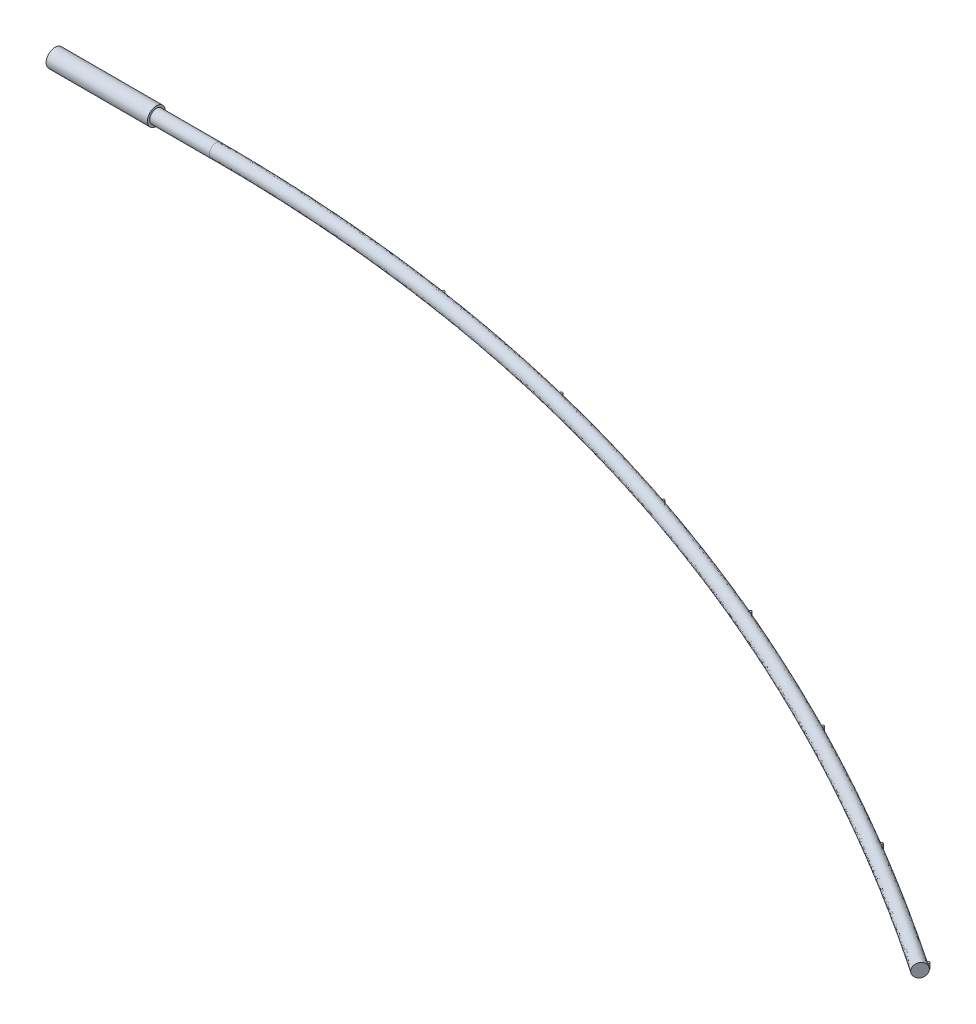
SolidWorks part; units mm, degrees
ref_plane "Front Plane" through (0, 0, 0) normal (0, 0, 1) x (1, 0, 0)
ref_plane "Top Plane" through (0, 0, 0) normal (0, 1, 0) x (1, 0, 0)
ref_plane "Right Plane" through (0, 0, 0) normal (1, 0, 0) x (0, 0, -1)
sketch "Sketch2" plane through (0, 0, 0) normal (1, 0, 0) x (0, 0, -1)
  circle A0 centre (0, 0) radius 1.5
  dimension "D1" = 3
extrude "Boss-Extrude1" add sketch "Sketch2" against normal blind 17
sketch "Sketch4" plane through (0, 0, 0) normal (0, 1, 0) x (1, 0, 0)
  line L0 (0, 0) -> (10, 0)
  dimension "D1" = 10
sketch "Sketch5" plane through (0, 0, 0) normal (1, 0, 0) x (0, 0, -1)
  line L0 (0, 0) -> (0, 1.125) construction
  circle A0 centre (0, 0) radius 1.125
  dimension "D1" = 1.125
sweep "Sweep2" add profiles "Sketch5" path "Sketch4"
sketch "Sketch3" plane through (0, 0, 0) normal (0, 1, 0) x (1, 0, 0)
  line L1 (10, -1.125) -> (10, 1.125) construction
  spline S0 degree 2 poles (-7.7999, -0.6016) (97.9101, 6.535) (203.6272, -70.9884) knots 0 0 0 1 1 1 construction
  spline S1 degree 2 poles (10, 0) (99, 0.0075) (188.005, -59.9946) knots 0.084192 0.084192 0.084192 0.926113 0.926113 0.926113
sketch "Sketch1" plane through (10, 0, 0) normal (1, 0, 0) x (0, 0, -1)
  line L0 (0, 0) -> (0, 1.125) construction
  circle A0 centre (0, 0) radius 1.125
  dimension "D1" = 1.125
sweep "Sweep3" add profiles "Sketch1" path "Sketch3"
sketch "Sketch6" plane through (0, 0, 0) normal (0, 1, 0) x (1, 0, 0)
  line L0 (50.0173, -1.8928) -> (49.6818, -4.1158)
  line L1 (98.7348, -13.7208) -> (98.022, -15.8507)
  line L2 (144.9161, -33.2009) -> (143.8965, -35.2041)
  line L3 (188.063, -58.6775) -> (186.8081, -60.5451)
  line L4 (74.6352, -6.7507) -> (74.1032, -8.9334)
  line L5 (122.1884, -22.608) -> (121.3129, -24.6769)
  line L6 (166.8766, -45.2889) -> (165.7309, -47.2245)
  circle A0 centre (50.0173, -1.8928) radius 0.2
  circle A1 centre (98.7348, -13.7208) radius 0.2
  circle A2 centre (144.9161, -33.2009) radius 0.2
  circle A3 centre (188.063, -58.6775) radius 0.2
  circle A4 centre (74.6352, -6.7507) radius 0.2
  circle A5 centre (122.1884, -22.608) radius 0.2
  circle A6 centre (166.8766, -45.2889) radius 0.2
  spline S0 degree 3 poles (188.634, -59.0618) (129.1532, -18.9633) (69.5862, 1.13) (10, 1.125) knots 0 0 0 0 1 1 1 1 weights 1 1 1 1 construction
  spline S1 degree 3 poles (10, -1.125) (69.0805, -1.12) (128.1835, -21.0232) (187.3761, -60.9274) knots 0 0 0 0 1 1 1 1 weights 1 1 1 1 construction
  point P0 (49.849, -3.008)
  point P9 (98.376, -14.793)
  point P12 (187.427, -59.624)
  point P16 (144.401, -34.213)
  point P20 (74.368, -7.847)
  point P23 (121.747, -23.651)
  point P28 (166.297, -46.268)
  dimension "D1" = 0.4
  dimension "D2" = 0.4
  dimension "D3" = 0.4
  dimension "D4" = 0.4
  dimension "D5" = 0.4
  dimension "D6" = 0.4
  dimension "D7" = 0.4
extrude "Boss-Extrude2" add sketch "Sketch6" along normal blind 0.5 and the other way blind 0.5 contours A1 | A0 | A2 | A3 | A4 | A5 | A6 region at (50.144, 0, 2.0401) region at (98.8484, 0, 13.8785) region at (145.0177, 0, 33.3666) region at (188.1544, 0, 58.8491) region at (74.7553, 0, 6.9035) region at (122.2957, 0, 22.77) region at (166.9728, 0, 45.4577)
equation "\"L\"=200"
equation "\"num_design_vars\"=20"
